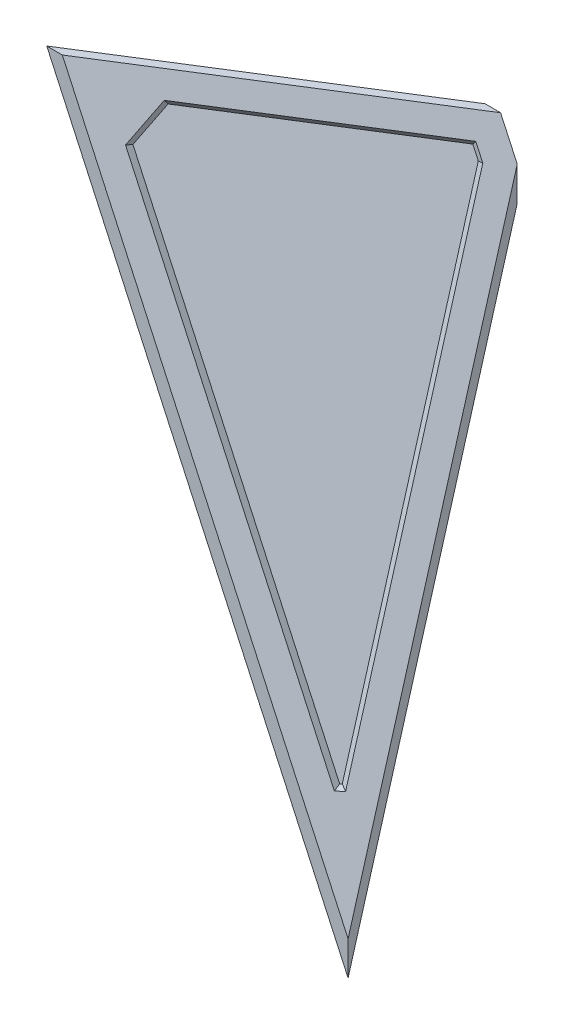
SolidWorks part; units mm, degrees
ref_plane "Plan de face" through (0, 0, 0) normal (0, 0, 1) x (1, 0, 0)
ref_plane "Plan de dessus" through (0, 0, 0) normal (0, 1, 0) x (1, 0, 0)
ref_plane "Plan de droite" through (0, 0, 0) normal (1, 0, 0) x (0, 0, -1)
sketch "Esquisse1" plane through (0, 0, 0) normal (0, 0, 1) x (1, 0, 0)
  line L0 (0, 0) -> (0, 815)
  line L1 (0, 815) -> (-374.0984, 815)
  line L2 (-374.0984, 815) -> (0, 0)
  line L3 (-374.0984, 815) -> (-420, 915) construction
  line L4 (-420, 915) -> (0, 915) construction
  line L5 (0, 915) -> (0, 815) construction
  dimension "D1" = 915
  dimension "D2" = 420
  dimension "D3" = 815
extrude "Boss.-Extru.1" add sketch "Esquisse1" against normal blind 210
sketch "Esquisse4" plane through (0, 815, 0) normal (0, 1, 0) x (1, 0, 0)
  line L0 (-40, 210) -> (-374.0984, 0)
  line L1 (-374.0984, 0) -> (-374.0984, 210)
  line L2 (-374.0984, 210) -> (-40, 210)
  line L3 (0, 210) -> (-374.0984, 210) construction
  line L4 (0, 210) -> (0, 0) construction
  dimension "D1" = 40
extrude "Enlèv. mat.-Extru.4" cut sketch "Esquisse4" against normal through all
ref_plane "Plan2" through (0, 0, 0) normal (-0.517, -0.2373, -0.8225) x (-0.856, 0.1433, 0.4967)
sketch "Esquisse5" plane through (0, 0, 0) normal (-0.517, -0.2373, -0.8225) x (-0.856, 0.1433, 0.4967)
  line L0 (437.0269, 783.0594) -> (0, 0)
  line L1 (0, 0) -> (-104.3076, 58.2143)
  line L2 (-104.3076, 58.2143) -> (12.4883, 841.2737)
  line L3 (12.4883, 841.2737) -> (46.7286, 841.2737)
  line L4 (46.7286, 841.2737) -> (437.0269, 783.0594)
extrude "Enlèv. mat.-Extru.5" cut sketch "Esquisse5" along normal through all
ref_plane "Plan3" through (5.1696, 2.3729, 8.2246) normal (-0.517, -0.2373, -0.8225) x (-0.856, 0.1433, 0.4967)
sketch "Esquisse6" plane through (5.1696, 2.3729, 8.2246) normal (-0.517, -0.2373, -0.8225) x (-0.856, 0.1433, 0.4967)
  line L0 (437.0269, 783.0594) -> (46.7286, 841.2737)
  line L1 (46.7286, 841.2737) -> (12.4883, 841.2737)
  line L2 (12.4883, 841.2737) -> (0, 757.5461)
  line L3 (0, 757.5461) -> (0, 0)
  line L4 (0, 0) -> (437.0269, 783.0594)
extrude "Enlèv. mat.-Extru.6" cut sketch "Esquisse6" against normal through all
sketch "Esquisse7" plane through (5.1696, 2.3729, 8.2246) normal (0.517, 0.2373, 0.8225) x (0.856, -0.1433, -0.4967)
  line L4 (-45.7861, 173.2665) -> (-36.0392, 175.8023)
  line L5 (-323.6724, 767.165) -> (-348.7583, 716.1284)
  line L8 (-36.0392, 155.8023) -> (-36.0392, 790.2313)
  line L9 (-36.0392, 790.2313) -> (-46.2586, 808.5422)
  line L10 (-46.2586, 808.5422) -> (-373.1253, 759.789)
  line L11 (-373.1253, 759.789) -> (-36.0392, 155.8023)
  line L12 (-36.0392, 175.8023) -> (-36.0392, 790.2313)
  line L13 (-36.0392, 790.2313) -> (-46.2586, 808.5422)
  line L14 (-46.2586, 808.5422) -> (-323.6724, 767.165)
  line L15 (-348.7583, 716.1284) -> (-45.7861, 173.2665)
  dimension "D1" = 30
extrude "Enlèv. mat.-Extru.7" cut sketch "Esquisse7" against normal blind 5
chamfer "Chanfrein1" distance 5 angle 45 6 edges at (-32.4367, 174.7438, -23.9491) (-166.2816, 456.7265, -21.177) (-285.218, 761.9497, -34.4811) (-155.747, 784.6704, -122.4164) (-32.639, 775.1415, -197.0476) (-28.265, 470.4381, -111.8844)
